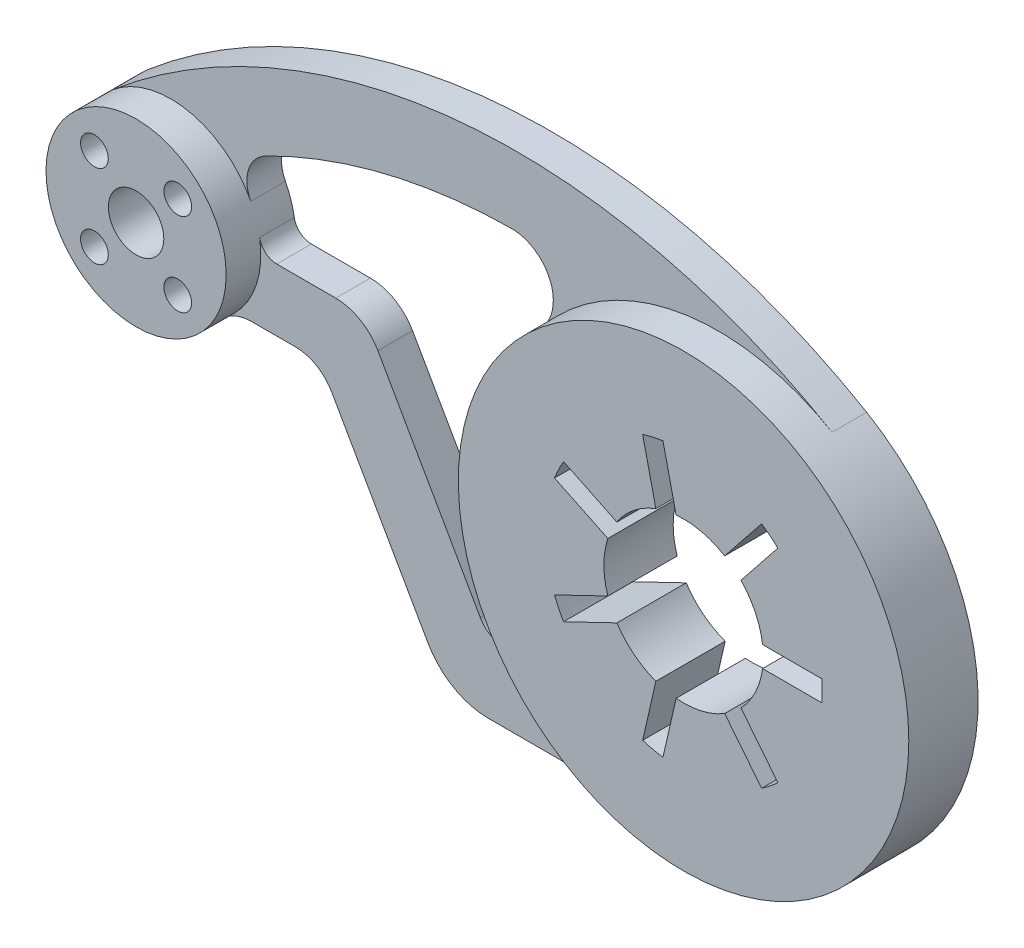
SolidWorks part; units mm, degrees
ref_plane "Спереди" through (0, 0, 0) normal (0, 0, 1) x (1, 0, 0)
ref_plane "Сверху" through (0, 0, 0) normal (0, 1, 0) x (1, 0, 0)
ref_plane "Справа" through (0, 0, 0) normal (1, 0, 0) x (0, 0, -1)
sketch "Эскиз2" plane through (0, 0, 0) normal (0, 0, 1) x (1, 0, 0)
  line L0 (0, -96.8468) -> (0, 88.6132) construction
  line L2 (39.8873, 3) -> (22.8035, 3)
  line L3 (39.8873, -3) -> (22.8035, -3)
  line L4 (156.2308, 0) -> (-209.9432, 0) construction
  line L5 (27.2148, -29.3147) -> (16.5632, -15.958)
  line L6 (22.5239, -33.0556) -> (11.8723, -19.699)
  line L7 (-5.951, -39.5548) -> (-2.1495, -22.8993)
  line L8 (-11.8006, -38.2197) -> (-7.999, -21.5642)
  line L9 (-34.6356, -20.0094) -> (-19.2436, -12.597)
  line L10 (-37.2389, -14.6036) -> (-21.8469, -7.1912)
  line L11 (-37.2389, 14.6036) -> (-21.8469, 7.1912)
  line L12 (-34.6356, 20.0094) -> (-19.2436, 12.597)
  line L13 (-11.8006, 38.2197) -> (-7.999, 21.5642)
  line L14 (-5.951, 39.5548) -> (-2.1495, 22.8993)
  line L15 (22.5239, 33.0556) -> (11.8723, 19.699)
  line L16 (27.2148, 29.3147) -> (16.5632, 15.958)
  line L17 (0, 0) -> (22.8035, -3) construction
  line L18 (0, -65) -> (-66.3714, -65)
  line L19 (-83.7527, -54.894) -> (-111.5484, -6.0636)
  line L20 (-161.9599, 18) -> (-66.0168, 18) construction
  line L21 (-134.6762, 0) -> (-121.9772, 0)
  line L22 (-115, 0) -> (-111.3863, 0) construction
  line L23 (-98.206, 10.9258) -> (-68.6724, -40.9576)
  line L24 (-127.4059, 18) -> (-110.3729, 18)
  line L25 (-158, 18) -> (-158, 74.7343) construction
  line L26 (-158, 18) -> (-197.6476, 57.6476) construction
  line L27 (-158, 18) -> (-170.0208, 30.0208) construction
  line L28 (-61.7199, -45) -> (-57.4456, -45)
  circle A0 centre (0, 0) radius 65
  arc A1 (-7.999, 21.5642) -> (-19.2436, 12.597) centre (0, 0) ccw
  arc A2 (39.8873, -3) -> (39.8873, 3) centre (0, 0) ccw
  arc A3 (22.5239, -33.0556) -> (27.2148, -29.3147) centre (0, 0) ccw
  arc A4 (-11.8006, -38.2197) -> (-5.951, -39.5548) centre (0, 0) ccw
  arc A5 (-37.2389, -14.6036) -> (-34.6356, -20.0094) centre (0, 0) ccw
  arc A6 (-34.6356, 20.0094) -> (-37.2389, 14.6036) centre (0, 0) ccw
  arc A7 (-5.951, 39.5548) -> (-11.8006, 38.2197) centre (0, 0) ccw
  arc A8 (27.2148, 29.3147) -> (22.5239, 33.0556) centre (0, 0) ccw
  arc A9 (11.8723, 19.699) -> (-2.1495, 22.8993) centre (0, 0) ccw
  arc A10 (22.8035, 3) -> (16.5632, 15.958) centre (0, 0) ccw
  arc A11 (16.5632, -15.958) -> (22.8035, -3) centre (0, 0) ccw
  arc A12 (-2.1495, -22.8993) -> (11.8723, -19.699) centre (0, 0) ccw
  arc A13 (-19.2436, -12.597) -> (-7.999, -21.5642) centre (0, 0) ccw
  arc A14 (-21.8469, 7.1912) -> (-21.8469, -7.1912) centre (0, 0) ccw
  circle A15 centre (-158, 18) radius 26
  arc A16 (-83.7527, -54.894) -> (-66.3714, -65) centre (-66.3714, -45) ccw
  arc A17 (-111.5484, -6.0636) -> (-121.9772, 0) centre (-121.9772, -12) ccw
  arc A18 (-98.206, 10.9258) -> (-110.3729, 18) centre (-110.3729, 4) ccw
  circle A19 centre (-170.0208, 30.0208) radius 4
  circle A20 centre (-145.9792, 30.0208) radius 4
  circle A21 centre (-145.9792, 5.9792) radius 4
  circle A22 centre (-170.0208, 5.9792) radius 4
  circle A23 centre (-158, 18) radius 8
  arc A24 (32.8562, 56.0845) -> (-176.4349, 36.4349) centre (-58.1302, -99.2264) ccw
  arc A25 (-61.7199, -45) -> (-68.6724, -40.9576) centre (-61.7199, -37) cw
  arc A26 (-57.4456, -45) -> (-53.3424, -37.1429) centre (-57.4456, -40) ccw
  arc A27 (-134.6762, 0) -> (-142.0416, -2.5263) centre (-134.6762, -12) ccw
  arc A28 (-132.3404, 22.1935) -> (-127.4059, 18) centre (-127.4059, 23) ccw
  arc A29 (-50.3023, 41.1665) -> (-59.7072, 60.7658) centre (-59.5889, 48.7664) ccw
  arc A30 (-130.5458, 43.448) -> (-134.9032, 29.9389) centre (-126.0198, 34.5309) ccw
  arc A33 (-59.7072, 60.7658) -> (-130.5458, 43.448) centre (-58.1302, -99.2264) ccw
  point P53 (-78, -65)
  point P59 (-102.2329, 18)
  dimension "D1" = 130
  dimension "D2" = 46
  dimension "D3" = 40
  dimension "D8" = 43
  dimension "D9" = 52
  dimension "D11" = 20
  dimension "D12" = 12
  dimension "D13" = 14
  dimension "D15" = 8
  dimension "D17" = 16
  dimension "D18" = 180
  dimension "D20" = 8
  dimension "D21" = 10
  dimension "D22" = 12
  dimension "D23" = 5
  dimension "D24" = 160
  dimension "D25" = 12
  dimension "D26" = 10
  dimension "D4" = 6
  dimension "D5" = 78
  dimension "D6" = 37
  dimension "D7" = 18
  dimension "D10" = 20
  dimension "D14" = 45
  dimension "D16" = 17
  dimension "D19" = 20
extrude "Бобышка-Вытянуть1" add sketch "Эскиз2" along normal blind 10 contours A33 A29 A0 A24 A15 A30 | A28 A15 A27 L21 A17 L19 A16 L18 A0 A26 L28 A25 L23 A18 L24 region at (-84.0189, -27.3538, 0) region at (-79.9164, 63.4061, 0)
extrude "Бобышка-Вытянуть2" add sketch "Эскиз2<3>" along normal blind 20 contours A15 A23 A22 A21 A20 A19 | A0 A14 L11 A6 L12 A1 L13 A7 L14 A9 L15 A8 L16 A10 L2 A2 L3 A11 L5 A3 L6 A12 L7 A4 L8 A13 L9 A5 L10 region at (-29.2381, -55.9867, 0) region at (-153.1282, 42.7904, 0)
sketch "Эскиз2<3>" plane through (0, 0, 0) normal (0, 0, 1) x (1, 0, 0) same geometry as "Эскиз2"
